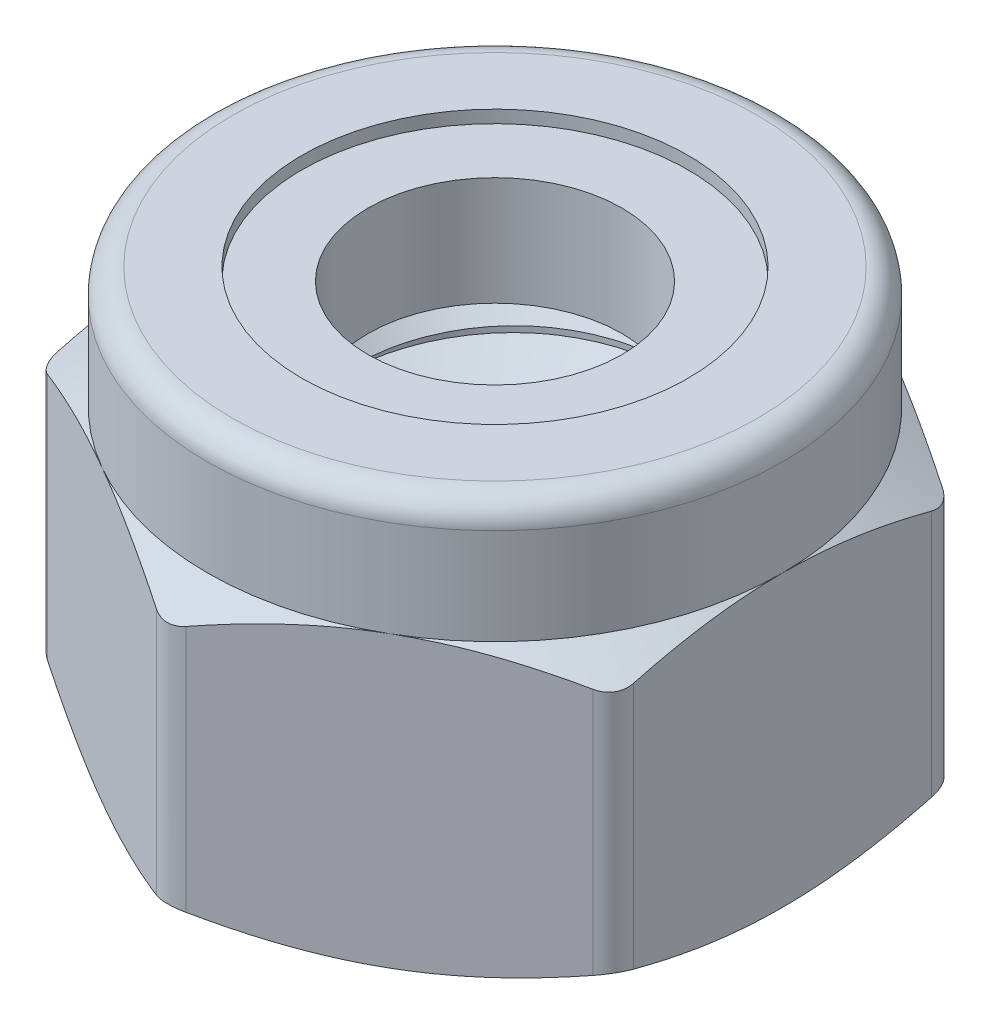
SolidWorks part; units mm, degrees
ref_plane "Front Plane" through (0, 0, 0) normal (0, 0, 1) x (1, 0, 0)
ref_plane "Top Plane" through (0, 0, 0) normal (0, 1, 0) x (1, 0, 0)
ref_plane "Right Plane" through (0, 0, 0) normal (1, 0, 0) x (0, 0, -1)
sketch "Sketch1" plane through (0, 0, 0) normal (0, 0, 1) x (1, 0, 0)
  line L0 (-3.5, -2.5) -> (3.5, -2.5) construction
  line L1 (-3.5, -2.5) -> (-3.5, 1.0242) construction
  line L2 (-3.5, 1.0242) -> (3.5, 1.0242) construction
  line L7 (3.5, 1.0242) -> (3.5, -2.5) construction
  line L8 (0, 2.5) -> (0, -2.5) construction
  line L9 (-2, 2.5) -> (-2, -2.5) construction
  line L10 (2, 2.5) -> (2, -2.5) construction
  line L11 (-2, 2.5) -> (2, 2.5) construction
  line L14 (3.5, -2.5) -> (4.0406, -2.1879) construction
  line L15 (3.5, 1.0242) -> (3.5, 2.5) construction
  line L16 (3.5, 2.5) -> (2, 2.5) construction
  line L17 (4.0406, -2.1879) -> (4.0406, 0.7121) construction
  line L18 (-3.5, 1.0242) -> (-3.5, 2.5) construction
  line L19 (-3.5, 2.5) -> (-2, 2.5) construction
  line L20 (4.0406, 0.7121) -> (3.5, 1.0242) construction
  line L21 (-2, -2.5) -> (-2, -3.1125) construction
  line L22 (-2, -3.1125) -> (-1.4696, -2.8063) construction
  line L23 (-1.4696, -2.8063) -> (-2, -2.5) construction
  line L24 (-2.0758, -2.4563) -> (-2.0758, -3.1563) construction
  line L25 (-2.0758, -2.4563) -> (-2, -2.5) construction
  line L26 (-2, -3.1125) -> (-2.0758, -3.1563) construction
  line L27 (-1.5453, -2.7625) -> (-1.5453, -2.85) construction
  line L28 (-2, -2.8063) -> (-2.0758, -2.8063) construction
  line L29 (-1.5453, -2.8063) -> (-1.4696, -2.8063) construction
  dimension "Width | s" = 7
  dimension "Thread Diameter" = 4
  dimension "Height | h" = 5
  dimension "D1" = 8.0811
  dimension "D2" = 30
  dimension "Flats Height" = 2.9
  dimension "Thread Pitch" = 0.7
  dimension "D4" = 0.0875
sketch "Sketch2" plane through (0, 0, 0) normal (0, 1, 0) x (1, 0, 0)
  line L0 (0, 0) -> (1.75, 3.0311) construction
  line L1 (3.5, 2.0207) -> (0, 4.0415)
  line L2 (0, 4.0415) -> (-3.5, 2.0207)
  line L3 (-3.5, 2.0207) -> (-3.5, -2.0207)
  line L4 (-3.5, -2.0207) -> (0, -4.0415)
  line L5 (0, -4.0415) -> (3.5, -2.0207)
  line L6 (3.5, -2.0207) -> (3.5, 2.0207)
  line L7 (0, 0) -> (3.5, 2.0207) construction
  circle A0 centre (0, 0) radius 3.5 construction
  circle A1 centre (0, 0) radius 4.0415 construction
extrude "Boss-Extrude1" add sketch "Sketch2" against normal up to vertex (2.5 mm away) from vertex up to point (3.5, -2.5, 0) starting at point (3.5, 1.0242, 0)
sketch "Sketch3" plane through (0, 0, 0) normal (0, 0, 1) x (1, 0, 0)
  line L3 (2, 1.8902) -> (4.0506, 0.7063)
  line L4 (2, 2.5) -> (2, -2.5) construction
  line L5 (2, -3.366) -> (4.0506, -2.1821)
  line L6 (4.0506, -2.1821) -> (4.0506, -3.366)
  line L7 (4.0506, -3.366) -> (2, -3.366)
  line L8 (2, 1.8902) -> (4.0506, 1.8902)
  line L10 (4.0506, 0.7063) -> (4.0506, 1.8902)
  dimension "D1" = 0.01
revolve "Cut-Revolve1" cut sketch "Sketch3" angle 360 about L8
fillet "Fillet1" radius 0.3604 6 edges at (-3.5, -0.7379, -2.0207) (-3.5, -0.7379, 2.0207) (0, -0.7379, 4.0415) (0, -0.7379, -4.0415) (3.5, -0.7379, -2.0207) (3.5, -0.7379, 2.0207)
sketch "Sketch5" plane through (0, 0, 0) normal (0, 0, 1) x (1, 0, 0)
  line L0 (-2.35, -2.5) -> (-2, -2.15)
  line L1 (-3.5, -2.5) -> (3.5, -2.5) construction
  line L2 (-2, 2.5) -> (-2, -2.5) construction
  line L3 (-2, -2.15) -> (-2, 0.6742)
  line L4 (-2, 0.6742) -> (-2.35, 1.0242)
  line L5 (-3.5, 1.0242) -> (3.5, 1.0242) construction
  line L6 (-2.35, 1.0242) -> (0, 1.0242)
  line L7 (0, 1.0242) -> (0, -2.5)
  line L8 (0, -2.5) -> (-2.35, -2.5)
  line L9 (0, 2.5) -> (0, -2.5) construction
  dimension "D1" = 45
  dimension "D2" = 0.35
revolve "Cut-Revolve2" cut sketch "Sketch5" angle 360 about L8
sketch "Sketch4" plane through (0, 0, 0) normal (0, 0, 1) x (1, 0, 0)
  line L0 (-2.35, 2.5) -> (-3.1937, 2.5)
  line L1 (-3.5, 2.5) -> (-2, 2.5) construction
  line L2 (-3.5, 2.1938) -> (-3.5, 1.0242)
  line L4 (-3.1937, 2.5) -> (-3.1937, 2.1938) construction
  line L5 (-1.7348, -2.6531) -> (-1.7348, -2.9594) construction
  line L6 (-1.4696, -2.8063) -> (-2, -2.5) construction
  line L7 (-2, -3.1125) -> (-1.4696, -2.8063) construction
  line L8 (-3.5, 1.0242) -> (-3.3469, 1.0242)
  line L10 (-2.35, 2.3469) -> (-2.35, 2.5)
  line L11 (-2.35, 2.3469) -> (-3.1937, 2.3469)
  line L12 (-3.3469, 2.1938) -> (-3.3469, 1.0242)
  arc A0 (-3.5, 2.1938) -> (-3.1937, 2.5) centre (-3.1937, 2.1938) cw
  arc A1 (-3.1937, 2.3469) -> (-3.3469, 2.1938) centre (-3.1937, 2.1938) ccw
revolve "Revolve1" add sketch "Sketch4" angle 360 about L8
sketch "Sketch6" plane through (0, 0, 0) normal (0, 0, 1) x (1, 0, 0)
  line L0 (-3.5, 1.0242) -> (3.5, 1.0242) construction
  line L1 (-3.1937, 2.3469) -> (-1.5453, 2.3469)
  line L2 (-3.3469, 2.1938) -> (-3.3469, 1.0242)
  line L3 (-3.3469, 1.0242) -> (-1.5453, 1.0242)
  line L4 (-1.5453, 2.3469) -> (-1.5453, 1.0242)
  arc A0 (-3.1937, 2.3469) -> (-3.3469, 2.1938) centre (-3.1937, 2.1938) ccw
revolve "Revolve2" add sketch "Sketch6" angle 360 about L8
sketch "Sketch7" plane through (0, -2.5, 0) normal (0, 1, 0) x (-1, 0, 0)
  line L0 (2, 0) -> (-2, 0) construction
  line L1 (0, 0) -> (-1.4142, -1.4142) construction
  circle A0 centre (0, 0) radius 2
  point P7 (-1.4142, -1.4142)
  dimension "D1" = 225
curve "Helix/Spiral1" pitch 0.7 height 5 radius 2 left hand yes centre (0, -2.5, 0) axis (0, 1, 0) start towards (0, 0, 1)
sketch "Sketch8" plane through (0, 0, 0) normal (0, 0, 1) x (1, 0, 0)
  line L0 (-2.0379, -2.4781) -> (-2.0379, -3.1344)
  line L1 (-2.0758, -2.4563) -> (-2, -2.5) construction
  line L2 (-2, -3.1125) -> (-2.0758, -3.1563) construction
  line L3 (-2.0379, -3.1344) -> (-1.5453, -2.85)
  line L4 (-1.5453, -2.85) -> (-1.5453, -2.7625)
  line L5 (-1.5453, -2.7625) -> (-2.0379, -2.4781)
sweep "Sweep1" add profiles "Sketch8" path "Helix/Spiral1"
sketch "Sketch9" plane through (0, 0, 0) normal (0, 0, 1) x (1, 0, 0)
  line L0 (-2.35, 2.6531) -> (-2.35, 1.0242)
  line L1 (-2.35, 1.0242) -> (-1.4696, 0.1437)
  line L2 (-1.4696, 0.1437) -> (-1.4696, 2.6531)
  line L4 (-1.4696, 2.6531) -> (-2.35, 2.6531)
  line L5 (-1.4696, -1.6196) -> (-2.35, -2.5)
  line L6 (-2.35, -2.5) -> (-2.35, -3.1563)
  line L7 (-2.35, -3.1563) -> (-1.4696, -3.1563)
  line L8 (-1.4696, -3.1563) -> (-1.4696, -1.6196)
  line L9 (-1.9098, 2.6531) -> (-1.9098, 2.5) construction
  line L10 (-2, 2.5) -> (2, 2.5) construction
  line L12 (-2.35, 2.3469) -> (-2.35, 2.5) construction
revolve "Cut-Revolve3" cut sketch "Sketch9" angle 360 about L8
equation "\"D1@Sketch1\"=\"Width | s@Sketch1\"*(1.15+.04/9)"
equation "\"D1@Fillet1\"=(\"D1@Sketch1\"-\"Width | s@Sketch1\")/3"
equation "\"D4@Sketch1\" = \"Thread Pitch@Sketch1\" / 8"
equation "\"D2@Sketch5\"=\"Thread Pitch@Sketch1\"*.5"
equation "\"D3@Helix/Spiral1\"=\"Height | h@Sketch1\""
equation "\"D4@Helix/Spiral1\"=\"Thread Pitch@Sketch1\""
